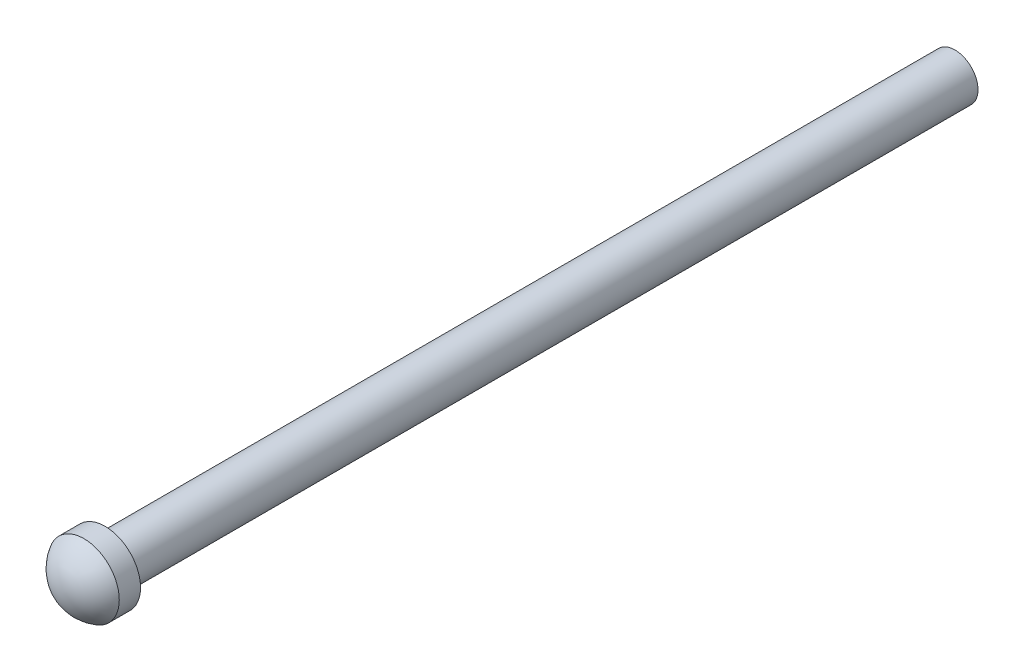
SolidWorks part; units mm, degrees
ref_plane "Front" through (0, 0, 0) normal (0, 0, 1) x (1, 0, 0)
ref_plane "Top" through (0, 0, 0) normal (0, 1, 0) x (1, 0, 0)
ref_plane "Right" through (0, 0, 0) normal (1, 0, 0) x (0, 0, -1)
sketch "草图1" plane through (0, 0, 0) normal (0, 0, 1) x (1, 0, 0)
  circle A2 centre (5, 60) radius 3.25
  circle A3 centre (5, 60) radius 3.25
  dimension "D1" = 0.25
sketch "草图2" plane through (0, 0, 0) normal (1, 0, 0) x (0, 0, -1)
  line L0 (0, 0) -> (120, 0) construction
  line L1 (0, 0) -> (120, 0)
sweep "扫描1" add profiles "草图1" path "草图2"
sketch "草图3" plane through (0, 0, 0) normal (0, 0, 1) x (1, 0, 0)
  circle A0 centre (5, 60) radius 5
extrude "凸台-拉伸1" add sketch "草图3" along normal blind 3
dome "圆顶1" faces to dome 1 distance 3 reverse direction no elliptical dome no face at (10, 60, 3) parameters "D1"=3
